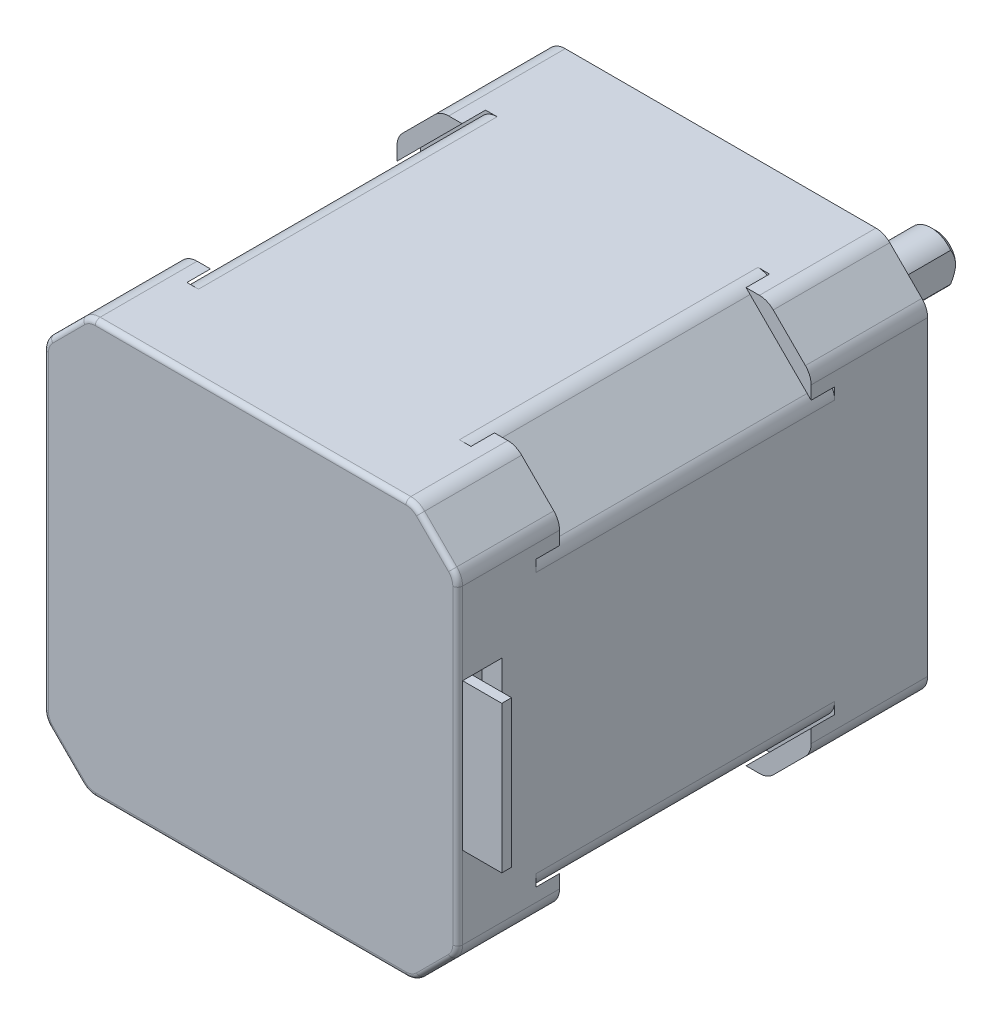
SolidWorks part; units mm, degrees
material "1060 Alloy"
ref_plane "Front Plane" through (0, 0, 0) normal (0, 0, 1) x (1, 0, 0)
ref_plane "Top Plane" through (0, 0, 0) normal (0, 1, 0) x (1, 0, 0)
ref_plane "Right Plane" through (0, 0, 0) normal (1, 0, 0) x (0, 0, -1)
ref_plane "Plane1"
sketch "Sketch1" plane through (0, 0, 0) normal (0, 0, 1) x (1, 0, 0)
  line L0 (-21.15, 21.15) -> (21.15, 21.15)
  line L1 (21.15, 21.15) -> (21.15, -21.15)
  line L2 (21.15, -21.15) -> (-21.15, -21.15)
  line L3 (-21.15, -21.15) -> (-21.15, 21.15)
  dimension "D1" = 42.3
  dimension "D2" = 42.3
extrude "Extrusion1" add sketch "Sketch1" along normal blind 48
chamfer "Chamfer1" distance 7 distance2 7 4 edges at (-21.15, 21.15, 24) (21.15, 21.15, 24) (-21.15, -21.15, 24) (21.15, -21.15, 24)
sketch "Sketch2" plane through (0, 0, 48) normal (0, 0, 1) x (1, 0, 0)
  line L0 (-14.15, 21.15) -> (-16.6956, 21.15)
  line L1 (-16.6956, 21.15) -> (-21.15, 16.6956)
  line L2 (-21.15, 16.6956) -> (-21.15, 14.15)
  line L3 (-21.15, 14.15) -> (-14.15, 21.15)
  line L4 (16.6956, 21.15) -> (14.15, 21.15)
  line L5 (14.15, 21.15) -> (21.15, 14.15)
  line L6 (21.15, 14.15) -> (21.15, 16.6956)
  line L7 (21.15, 16.6956) -> (16.6956, 21.15)
  line L8 (21.15, -16.6956) -> (21.15, -14.15)
  line L9 (21.15, -14.15) -> (14.15, -21.15)
  line L10 (14.15, -21.15) -> (16.6956, -21.15)
  line L11 (16.6956, -21.15) -> (21.15, -16.6956)
  line L12 (-16.6956, -21.15) -> (-14.15, -21.15)
  line L13 (-14.15, -21.15) -> (-21.15, -14.15)
  line L14 (-21.15, -14.15) -> (-21.15, -16.6956)
  line L15 (-21.15, -16.6956) -> (-16.6956, -21.15)
  line M2 (-14.15, 21.15) -> (-21.15, 14.15)
  line M4 (-21.15, -14.15) -> (-14.15, -21.15)
  line M6 (14.15, -21.15) -> (21.15, -14.15)
  line M8 (21.15, 14.15) -> (14.15, 21.15)
  dimension "D1" = 1.8
extrude "Extrusion2" add sketch "Sketch2" against normal blind 8 contours L1 L2 L0 M2 | L6 L7 L4 M8 | L10 L11 L8 M6 | L14 L15 L12 M4
sketch "Sketch3" plane through (0, 0, 0) normal (0, 0, -1) x (-1, 0, 0)
  line L0 (21.15, -14.15) -> (14.15, -21.15)
  line L1 (14.15, -21.15) -> (16.6956, -21.15)
  line L2 (16.6956, -21.15) -> (21.15, -16.6956)
  line L3 (21.15, -16.6956) -> (21.15, -14.15)
  line L4 (-21.15, 14.15) -> (-21.15, 16.6956)
  line L5 (-21.15, 16.6956) -> (-16.6956, 21.15)
  line L6 (-16.6956, 21.15) -> (-14.15, 21.15)
  line L7 (-14.15, 21.15) -> (-21.15, 14.15)
  line L8 (21.15, 16.6956) -> (16.6956, 21.15)
  line L9 (16.6956, 21.15) -> (14.15, 21.15)
  line L10 (14.15, 21.15) -> (21.15, 14.15)
  line L11 (21.15, 14.15) -> (21.15, 16.6956)
  line L12 (-14.15, -21.15) -> (-21.15, -14.15)
  line L13 (-21.15, -14.15) -> (-21.15, -16.6956)
  line L14 (-21.15, -16.6956) -> (-16.6956, -21.15)
  line L15 (-16.6956, -21.15) -> (-14.15, -21.15)
  line M2 (21.15, 14.15) -> (14.15, 21.15)
  line M4 (-14.15, 21.15) -> (-21.15, 14.15)
  line M6 (-21.15, -14.15) -> (-14.15, -21.15)
  line M8 (14.15, -21.15) -> (21.15, -14.15)
extrude "Extrusion3" add sketch "Sketch3" against normal blind 9.5 contours L2 L3 L1 M8 | L6 L5 L4 M4 | L11 L8 L9 M2 | L14 L15 L13 M6
ref_plane "Plane2"
sketch "Sketch4" plane through (0, 0, 40) normal (0, 0, -1) x (-1, 0, 0)
  line L0 (-21.15, -16.6956) -> (-16.6956, -21.15)
  line L1 (-16.6956, -21.15) -> (-14.5036, -21.15)
  line L2 (-14.5036, -21.15) -> (-21.15, -14.5036)
  line L3 (-21.15, -14.5036) -> (-21.15, -16.6956)
  line L4 (14.5036, -21.15) -> (21.15, -14.5036)
  line L5 (21.15, -14.5036) -> (21.15, -16.6956)
  line L6 (21.15, -16.6956) -> (16.6956, -21.15)
  line L7 (16.6956, -21.15) -> (14.5036, -21.15)
  line L8 (21.15, 14.5036) -> (14.5036, 21.15)
  line L9 (14.5036, 21.15) -> (16.6956, 21.15)
  line L10 (16.6956, 21.15) -> (21.15, 16.6956)
  line L11 (21.15, 16.6956) -> (21.15, 14.5036)
  line L12 (-14.5036, 21.15) -> (-21.15, 14.5036)
  line L13 (-21.15, 14.5036) -> (-21.15, 16.6956)
  line L14 (-21.15, 16.6956) -> (-16.6956, 21.15)
  line L15 (-16.6956, 21.15) -> (-14.5036, 21.15)
extrude "Extrusion4" add sketch "Sketch4" along normal blind 2.4 contours L2 L3 L0 L1 | L7 L6 L5 L4 | L11 L10 L9 L8 | L15 L14 L13 L12
ref_plane "Plane3"
sketch "Sketch5" plane through (0, 0, 9.5) normal (0, 0, 1) x (1, 0, 0)
  line L0 (21.15, 16.6956) -> (21.15, 14.5036)
  line L1 (21.15, 14.5036) -> (14.5036, 21.15)
  line L2 (14.5036, 21.15) -> (16.6956, 21.15)
  line L3 (16.6956, 21.15) -> (21.15, 16.6956)
  line L4 (-16.6956, 21.15) -> (-14.5036, 21.15)
  line L5 (-14.5036, 21.15) -> (-21.15, 14.5036)
  line L6 (-21.15, 14.5036) -> (-21.15, 16.6956)
  line L7 (-21.15, 16.6956) -> (-16.6956, 21.15)
  line L8 (21.15, -14.5036) -> (21.15, -16.6956)
  line L9 (21.15, -16.6956) -> (16.6956, -21.15)
  line L10 (16.6956, -21.15) -> (14.5036, -21.15)
  line L11 (14.5036, -21.15) -> (21.15, -14.5036)
  line L12 (-21.15, -16.6956) -> (-16.6956, -21.15)
  line L13 (-16.6956, -21.15) -> (-14.5036, -21.15)
  line L14 (-14.5036, -21.15) -> (-21.15, -14.5036)
  line L15 (-21.15, -14.5036) -> (-21.15, -16.6956)
extrude "Extrusion5" add sketch "Sketch5" along normal blind 2.4 contours L3 L2 L1 L0 | L7 L6 L5 L4 | L11 L10 L9 L8 | L14 L15 L12 L13
fillet "Fillet1" radius 0.5 8 edges at (-18.9228, -18.9228, 48) (-21.15, 0, 48) (-18.9228, 18.9228, 48) (18.9228, 18.9228, 48) (21.15, 0, 48) (18.9228, -18.9228, 48) (0, -21.15, 48) (0, 21.15, 48)
fillet "Fillet2" radius 2 32 edges at (16.6349, 21.0036, 47.8536) (21.0036, 16.6349, 47.8536) (-21.0036, 16.6349, 47.8536) (-16.6349, 21.0036, 47.8536) (-21.0036, -16.6349, 47.8536) (-16.6349, -21.0036, 47.8536) (21.0036, -16.6349, 47.8536) (16.6349, -21.0036, 47.8536) (16.6956, -21.15, 5.95) (21.15, -16.6956, 5.95) (16.6956, -21.15, 42.55) (21.15, -16.6956, 42.55) (21.15, -14.15, 24.75) (14.15, -21.15, 24.75) (-21.15, -16.6956, 5.95) (-16.6956, -21.15, 5.95) (-16.6956, -21.15, 42.55) (-21.15, -16.6956, 42.55) (-21.15, -14.15, 24.75) (-14.15, -21.15, 24.75) (-16.6956, 21.15, 42.55) (-21.15, 16.6956, 42.55) (-21.15, 16.6956, 5.95) (-16.6956, 21.15, 5.95) (21.15, 16.6956, 5.95) (16.6956, 21.15, 5.95) (21.15, 16.6956, 42.55) (16.6956, 21.15, 42.55) (21.15, 14.15, 24.75) (-21.15, 14.15, 24.75) (-14.15, 21.15, 24.75) (14.15, 21.15, 24.75)
sketch "Sketch6" plane through (0, 0, 0) normal (0, 0, -1) x (-1, 0, 0)
  circle A0 centre (0, 0) radius 11
  dimension "D1" = 22
extrude "Extrusion6" add sketch "Sketch6" along normal blind 2
ref_plane "Plane4"
sketch "Sketch7" plane through (0, 0, 0) normal (0, 0, -1) x (-1, 0, 0)
  circle A0 centre (0, 0) radius 16.25
  circle A1 centre (0, 0) radius 11
  dimension "D1" = 32.5
extrude "Extrusion7" cut sketch "Sketch7" against normal blind 0.4 contours A0 A1
sketch "Sketch8" plane through (0, 0, -2) normal (0, 0, -1) x (-1, 0, 0)
  circle A0 centre (0, 0) radius 2.5
  dimension "D1" = 5
extrude "Extrusion8" add sketch "Sketch8" along normal blind 20
chamfer "Chamfer2" distance 0.5 distance2 0.5 1 edges at (-2.5, 0, -22)
ref_plane "Plane5"
sketch "Sketch9" plane through (0, 0, -2) normal (0, 0, -1) x (-1, 0, 0)
  circle A0 centre (0, 0) radius 3.4
  circle A1 centre (0, 0) radius 2.5
  dimension "D1" = 6.8
extrude "Extrusion9" cut sketch "Sketch9" against normal blind 3 contours A0 A1
hole_wizard "Hole1" positions "Sketch11" profile "Sketch10" legacy
sketch "Sketch11" plane through (0, 0, 0) normal (0, 0, -1) x (-1, 0, 0)
  point P1 (-15.5, 15.5)
  point P2 (15.5, 15.5)
  point P3 (15.5, -15.5)
  point P4 (-15.5, -15.5)
sketch "Sketch10" plane through (15.5, 15.5, 0) normal (1, 0, 0) x (0, 1, 0)
  line L0 (0, 0) -> (0, 5.2388)
  line L1 (0, 5.2388) -> (1.2295, 4.5)
  line L2 (1.2295, 4.5) -> (1.2295, 0)
  line L4 (1.2295, 0) -> (0, 0)
  line L6 (0, 5.2388) -> (-1.2295, 4.5) construction
  line L7 (0, -4.2442) -> (0, 117.3081) construction
  dimension "Diameter" = 2.459
  dimension "Depth" = 4.5
  dimension "Drill Angle" = 118
cosmetic thread "Cosmetic Thread1" parameters "D1"=4.5, "D2"=31.72
cosmetic thread "Cosmetic Thread2" parameters "D1"=4.5, "D2"=31.72
cosmetic thread "Cosmetic Thread3" parameters "D1"=4.5, "D2"=31.72
cosmetic thread "Cosmetic Thread4" parameters "D1"=4.5, "D2"=31.72
sketch "Sketch12" plane through (0, 0, -22) normal (0, 0, -1) x (-1, 0, 0)
  line L0 (-2, -1.5) -> (-2, 1.5)
  arc A0 (-2, 1.5) -> (-2, -1.5) centre (0, 0) ccw
extrude "Extrusion10" cut sketch "Sketch12" against normal blind 20
sketch "Sketch13" plane through (21.15, 0, 0) normal (1, 0, 0) x (0, 0, -1)
  line L0 (-47.5, 7.5) -> (-47.5, -7.5)
  line L1 (-47.5, -7.5) -> (-43.5, -7.5)
  line L2 (-43.5, -7.5) -> (-43.5, 7.5)
  line L3 (-43.5, 7.5) -> (-47.5, 7.5)
  dimension "D1" = 15
  dimension "D2" = 4
extrude "Extrusion11" add sketch "Sketch13" along normal blind 4
ref_plane "Plane6"
sketch "Sketch14" plane through (25.15, 14.5036, 40) normal (1, 0, 0) x (0, 0, -1)
  line L0 (-3.5, -7.0036) -> (-6.5, -7.0036)
  line L1 (-6.5, -7.0036) -> (-6.5, -22.0036)
  line L2 (-6.5, -22.0036) -> (-3.5, -22.0036)
  line L3 (-3.5, -22.0036) -> (-3.5, -7.0036)
  dimension "D1" = 3
extrude "Extrusion12" cut sketch "Sketch14" against normal blind 6
